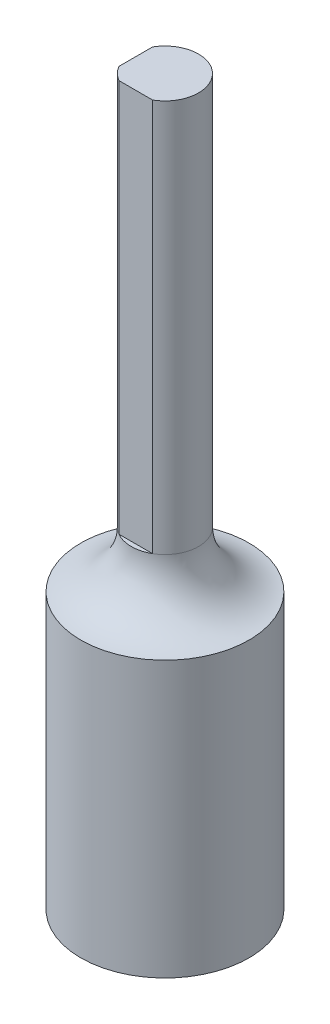
SolidWorks part; units mm, degrees
ref_plane "Front Plane" through (0, 0, 0) normal (0, 0, 1) x (1, 0, 0)
ref_plane "Top Plane" through (0, 0, 0) normal (0, 1, 0) x (1, 0, 0)
ref_plane "Right Plane" through (0, 0, 0) normal (1, 0, 0) x (0, 0, -1)
sketch "Sketch1" plane through (0, 0, 0) normal (0, 1, 0) x (1, 0, 0)
  line L0 (-1.52, 5.24) -> (1.52, 5.24)
  line L1 (-1.52, 5.24) -> (-1.52, 3.7054)
  line L2 (1.52, 5.24) -> (1.52, 3.7054)
  circle A0 centre (0, 0) radius 4.005
  circle A1 centre (0, 0) radius 7.5
  point P5 (0, 5.24)
  dimension "D1" = 8.01
  dimension "D4" = 15
  dimension "D2" = 3.04
  dimension "D3" = 5.24
extrude "Boss-Extrude1" add sketch "Sketch1" along normal blind 22 contours A1 A0 L1 L0 L2 region at (-7.2879, 0, 0)
sketch "Sketch3" plane through (0, 22, 0) normal (0, 1, 0) x (1, 0, 0)
  circle A0 centre (0, 0) radius 7.5
extrude "Boss-Extrude2" add sketch "Sketch3" along normal blind 2.54
sketch "Sketch4" plane through (0, 24.54, 0) normal (0, 1, 0) x (1, 0, 0)
  circle A0 centre (0, 0) radius 3
  dimension "D1" = 6
sketch "Sketch7" plane through (0, 24.54, 0) normal (0, 1, 0) x (1, 0, 0)
  point P0 (0, 0)
hole_wizard "M3 Clearance Hole1" positions "Sketch7" profile "Sketch6" hole size "M3" standard "ANSI Metric" end condition up to next
sketch "Sketch6" plane through (0, 24.54, 0) normal (1, 0, 0) x (0, 0, 1)
  line L0 (0, 0) -> (0, 2.54)
  line L1 (0, 2.54) -> (1.7, 2.54)
  line L2 (1.7, 2.54) -> (1.7, 0)
  line L5 (1.7, 0) -> (0, 0)
  line L11 (0, -6.35) -> (0, 107.95) construction
  dimension "Thru Hole Dia." = 3.4
  dimension "Thru Hole Depth" = 2.54
extrude "Boss-Extrude4" add sketch "Sketch4" along normal blind 40
ref_plane "Plane4" through (-3, 0, 0) normal (-1, 0, 0) x (0, 0, 1)
fillet "Fillet1" radius 5 1 edges at (0, 24.54, 3)
sketch "Sketch12" plane through (-3, 0, 0) normal (-1, 0, 0) x (0, 0, 1)
  line L0 (-3, 29.5149) -> (3, 29.5149) construction
  line L1 (-7.5, 29.5149) -> (7.5, 29.5149)
  line L2 (-7.5, 29.5149) -> (-7.5, 64.8388)
  line L3 (-7.5, 64.8388) -> (7.5, 64.8388)
  line L4 (7.5, 29.5149) -> (7.5, 64.8388)
extrude "Cut-Extrude1" cut sketch "Sketch12" against normal blind 0.4
pattern_circular "CirPattern2" count 2 every 90 about axis through (0, 64.54, 0) along (0, 1, 0) of "Cut-Extrude1"
